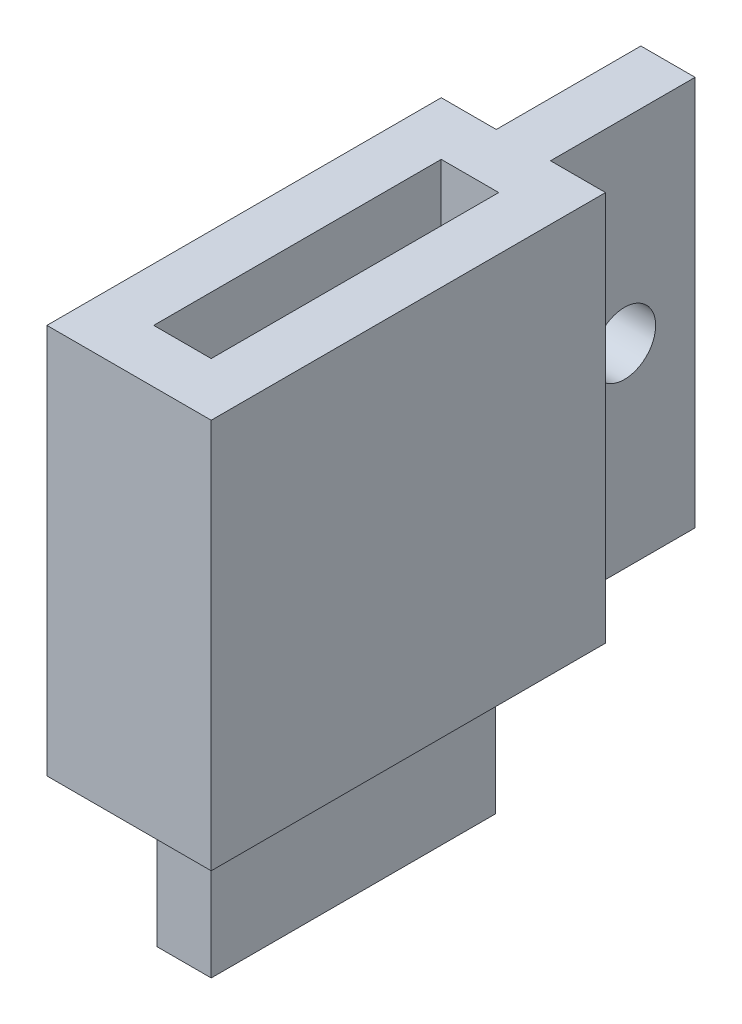
SolidWorks part; units mm, degrees
ref_plane "Front Plane" through (0, 0, 0) normal (1, 0, 0) x (0, 1, 0)
ref_plane "Top Plane" through (0, 0, 0) normal (0, 0, 1) x (0, 1, 0)
ref_plane "Right Plane" through (0, 0, 0) normal (0, 1, 0) x (-1, 0, 0)
sketch "Sketch1" plane through (0, 0, 0) normal (1, 0, 0) x (0, 1, 0)
  line L1 (0, 0) -> (23.75, 0)
  line L2 (0, 0) -> (0, 24)
  line L3 (0, 24) -> (23.75, 24)
  line L4 (23.75, 0) -> (23.75, 24)
  dimension "D1" = 23.75
  dimension "D2" = 24
extrude "Boss-Extrude1" add sketch "Sketch1" against normal blind 10
sketch "Sketch2" plane through (0, 0, 0) normal (0, -1, 0) x (1, 0, 0)
  line L1 (-10, 0) -> (-6.65, 0)
  line L2 (-10, 0) -> (-10, -8.8)
  line L3 (-10, -8.8) -> (-6.65, -8.8)
  line L4 (-6.65, 0) -> (-6.65, -8.8)
  line L5 (0, 0) -> (-3.35, 0)
  line L6 (0, 0) -> (0, -8.8)
  line L7 (0, -8.8) -> (-3.35, -8.8)
  line L8 (-3.35, 0) -> (-3.35, -8.8)
  line L9 (-6.65, -8.8) -> (-3.35, -8.8)
  line L10 (-6.65, -8.8) -> (-6.65, 0)
  line L11 (-6.65, 0) -> (-3.35, 0)
  line L12 (-3.35, -8.8) -> (-3.35, 0)
  line M12 (-10, 0) -> (0, 0)
  dimension "D1" = 8.8
  dimension "D2" = 3.35
  dimension "D3" = 3.35
extrude "Boss-Extrude2" add sketch "Sketch2" against normal through all contours L4 L9 L8 M12 region at (-5, 0, -4.4)
sketch "Sketch3" plane through (0, 0, 0) normal (0, -1, 0) x (1, 0, 0)
  line L0 (-3.35, 20.65) -> (-3.35, 3.35)
  line L1 (0, 24) -> (-10, 24)
  line L2 (0, 24) -> (0, 0)
  line L3 (0, 0) -> (-10, 0)
  line L4 (-10, 24) -> (-10, 0)
  line L5 (-3.35, 3.35) -> (-6.65, 3.35)
  line L6 (-6.65, 20.65) -> (-6.65, 3.35)
  line L7 (-3.35, 20.65) -> (-6.65, 20.65)
  dimension "D1" = 3.35
extrude "Boss-Extrude3" add sketch "Sketch3" along normal blind 9 contours L0 L7 L6 L5 region at (-5, 0, 12)
sketch "Sketch4" plane through (-6.65, 0, 0) normal (-1, 0, 0) x (0, -1, 0)
  line L0 (0, 0) -> (-23.75, 0) construction
  line L1 (-11.875, 0) -> (-23.75, 0)
  line L2 (-11.875, 0) -> (-11.875, -4.5)
  line L3 (-11.875, -4.5) -> (-23.75, -4.5)
  line L4 (-23.75, 0) -> (-23.75, -4.5)
  circle A0 centre (-11.875, -4.5) radius 1.9
  dimension "D2" = 3.8
  dimension "D1" = 4.5
extrude "Cut-Extrude1" cut sketch "Sketch4" against normal up to next contours A0
sketch "Sketch5" plane through (0, 23.75, 0) normal (0, 1, 0) x (-1, 0, 0)
  line L0 (3.25, 20.75) -> (3.25, 3.25)
  line L1 (0, 24) -> (10, 24)
  line L2 (0, 24) -> (0, 0)
  line L3 (0, 0) -> (10, 0)
  line L4 (10, 24) -> (10, 0)
  line L5 (3.25, 3.25) -> (6.75, 3.25)
  line L6 (6.75, 20.75) -> (6.75, 3.25)
  line L7 (3.25, 20.75) -> (6.75, 20.75)
  dimension "D1" = 3.25
extrude "Cut-Extrude2" cut sketch "Sketch5" against normal blind 9 contours L7 L0 L5 L6 region at (-5, 23.75, 12)
equation "\"whitekey_cutout_length\"= 101.5"
equation "\"key_mount_recess_length\"=50"
equation "\"key_mount_recess_height\"=12.5"
equation "\"key_mount_recess_depth\"=1.5"
equation "\"wall_thickness\"=10"
equation "\"guide_brace_height\"=20"
equation "\"guide_brace_thickness\"=2"
equation "\"dowel_recess_depth\"=9"
equation "\"dowel_recess_offset\"=3.25"
equation "\"base_mount_height\"=40"
equation "\"base_rear_length\"=80"
equation "\"base_front_length\"=111.5"
equation "\"screw_hole_wall_offset\"=7.25"
equation "\"screw_hole_edge_inset\"=4.5"
equation "\"screw_hole_diameter\"=3.8"
equation "\"screw_head_hole_diameter\"=6.7"
equation "\"screw_nut_hole_side_len\"=3.5"
equation "\"screw_shaft_diameter\"=3.5"
equation "\"switch_board_width\"=30"
equation "\"switch_board_wall_offset\"=11.5"
equation "\"heatset_insert_hole_diameter\"=4.8"
equation "\"heatset_insert_hole_depth\"=3.8"
equation "\"D1@Boss-Extrude1\"=\"wall_thickness\""
equation "\"D2@Sketch2\"=\"dowel_recess_offset\"+0.1"
equation "\"D3@Sketch2\"=\"dowel_recess_offset\"+0.1"
equation "\"D1@Boss-Extrude3\"=\"dowel_recess_depth\""
equation "\"D1@Sketch3\"=\"dowel_recess_offset\"+0.1"
equation "\"D1@Sketch2\"=\"dowel_recess_depth\"-0.2"
equation "\"D1@Sketch4\"=\"screw_hole_edge_inset\""
equation "\"D2@Sketch4\"=\"screw_hole_diameter\""
equation "\"D1@Sketch5\"=\"dowel_recess_offset\""
equation "\"D1@Cut-Extrude2\"=\"dowel_recess_depth\""
equation "\"screw_nut_recess_offset\"=0.4"
equation "\"screw_head_and_nut_recess_depth\"=2.5"
equation "\"front_rear_panel_width\"=23.75"
equation "\"rod_length_adj\"=0.5"
equation "\"rod_insert_length\"=2.8"
equation "\"D1@Sketch1\"=\"front_rear_panel_width\""
